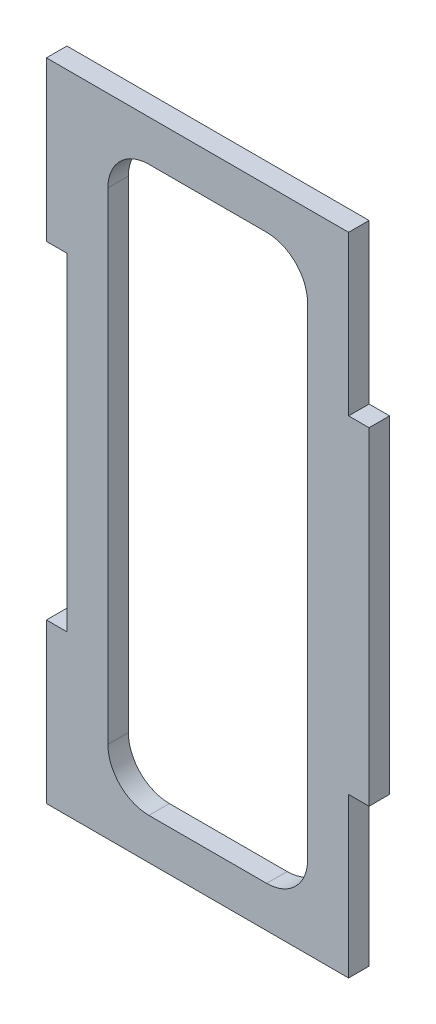
SolidWorks part; units mm, degrees
material "Acrylic (Medium-high impact)"
ref_plane "Front Plane" through (0, 0, 0) normal (0, 0, 1) x (1, 0, 0)
ref_plane "Top Plane" through (0, 0, 0) normal (0, 1, 0) x (1, 0, 0)
ref_plane "Right Plane" through (0, 0, 0) normal (1, 0, 0) x (0, 0, -1)
sketch "Sketch1" plane through (0, 0, 0) normal (0, 0, 1) x (1, 0, 0)
  line L1 (-50, -150.1518) -> (50, -150.1518)
  line L2 (-50, -150.1518) -> (-50, 50)
  line L3 (-50, 50) -> (50, 50)
  line L4 (50, -150.1518) -> (50, 50)
  dimension "D1" = 100
  dimension "D2" = 50
  dimension "D3" = 200.1518
  dimension "D4" = 50
extrude "Boss-Extrude1" add sketch "Sketch1" along normal blind 6.35
sketch "Sketch2" plane through (0, 0, 6.35) normal (0, 0, 1) x (1, 0, 0)
  line L0 (-43.65, 50) -> (-43.65, -150.1518) construction
  line L1 (50, 50) -> (-50, 50) construction
  line L2 (-50, -150.1518) -> (50, -150.1518) construction
  line L3 (-50, -50.0759) -> (50, -50.0759) construction
  line L4 (-50, 50) -> (-50, -150.1518) construction
  line L5 (50, -150.1518) -> (50, 50) construction
  line L6 (43.65, 50) -> (43.65, -150.1518) construction
  line L7 (-43.65, -50.0759) -> (-43.65, 50) construction
  line L8 (43.65, -50.0759) -> (43.65, 50) construction
  line L10 (-50, -50.0759) -> (-43.65, -50.0759)
  line L11 (-50, -50.0759) -> (-50, 0.7241)
  line L12 (-50, 0.7241) -> (-43.65, 0.7241)
  line L13 (-43.65, -50.0759) -> (-43.65, 0.7241)
  line L14 (-50, -50.0759) -> (-43.65, -50.0759)
  line L15 (-50, -50.0759) -> (-50, -100.8759)
  line L16 (-50, -100.8759) -> (-43.65, -100.8759)
  line L17 (-43.65, -50.0759) -> (-43.65, -100.8759)
  line L18 (43.65, 50) -> (50, 50)
  line L19 (43.65, 50) -> (43.65, 0.7241)
  line L20 (43.65, 0.7241) -> (50, 0.7241)
  line L21 (50, 50) -> (50, 0.7241)
  line L22 (43.65, -150.1518) -> (50, -150.1518)
  line L23 (43.65, -150.1518) -> (43.65, -100.8759)
  line L24 (43.65, -100.8759) -> (50, -100.8759)
  line L25 (50, -150.1518) -> (50, -100.8759)
  line M8 (-50, 50) -> (-50, -150.1518)
  line M9 (-50, -150.1518) -> (50, -150.1518)
  line M10 (50, -150.1518) -> (50, 50)
  line M11 (50, 50) -> (-50, 50)
  dimension "D1" = 6.35
  dimension "D2" = 6.35
  dimension "D3" = 100.0759
  dimension "D4" = 50.8
  dimension "D5" = 50.8
  dimension "D6" = 50.8
  dimension "D7" = 50.8
extrude "Cut-Extrude1" cut sketch "Sketch2" against normal blind 6.35 contours L10 L13 L12 M8 | L17 L10 L16 M8 | L19 L20 M10 M11 | L24 L23 M9 M10 region at (-46.825, -24.6759, 6.35) region at (-46.825, -75.4759, 6.35) region at (46.825, 25.3621, 6.35) region at (46.825, -125.5139, 6.35)
sketch "Sketch3" plane through (0, 0, 6.35) normal (0, 0, 1) x (1, 0, 0)
  line L0 (-43.65, -100.8759) -> (-43.65, 0.7241) construction
  line L1 (-30.95, -137.4518) -> (30.95, -137.4518)
  line L2 (-30.95, -137.4518) -> (-30.95, 37.3)
  line L3 (-30.95, 37.3) -> (30.95, 37.3)
  line L4 (30.95, -137.4518) -> (30.95, 37.3)
  line L5 (43.65, 50) -> (-50, 50) construction
  line L6 (43.65, 50) -> (43.65, 0.7241) construction
  line L7 (-50, -150.1518) -> (43.65, -150.1518) construction
  dimension "D1" = 12.7
  dimension "D2" = 12.7
  dimension "D3" = 12.7
  dimension "D4" = 12.7
extrude "Cut-Extrude2" cut sketch "Sketch3" against normal blind 6.35
fillet "Fillet1" radius 12.7 4 edges at (30.95, -137.4518, 3.175) (30.95, 37.3, 3.175) (-30.95, 37.3, 3.175) (-30.95, -137.4518, 3.175)
sketch "Sketch4" plane through (0, 0, 6.35) normal (0, 0, 1) x (1, 0, 0)
  line L0 (-30.95, 24.6) -> (-30.95, -124.7518)
  line L1 (-50, 50) -> (43.65, 50)
  line L2 (-50, 50) -> (-50, 0.7241)
  line L3 (-50, -150.1518) -> (43.65, -150.1518)
  line L4 (43.65, 50) -> (43.65, 0.7241)
  line L5 (50, -100.8759) -> (43.65, -100.8759)
  line L6 (50, -100.8759) -> (50, 0.7241)
  line L7 (50, 0.7241) -> (43.65, 0.7241)
  line L9 (-50, 0.7241) -> (-43.65, 0.7241)
  line L10 (43.65, -100.8759) -> (43.65, -150.1518)
  line L11 (-50, -100.8759) -> (-43.65, -100.8759)
  line L12 (-43.65, 0.7241) -> (-43.65, -100.8759)
  line L13 (30.95, 24.6) -> (30.95, -124.7518)
  line L14 (-18.25, 37.3) -> (18.25, 37.3)
  line L15 (18.25, -137.4518) -> (-18.25, -137.4518)
  line L16 (-50, -100.8759) -> (-50, -150.1518)
  arc A0 (-18.25, 37.3) -> (-30.95, 24.6) centre (-18.25, 24.6) ccw
  arc A1 (18.25, 37.3) -> (30.95, 24.6) centre (18.25, 24.6) cw
  arc A2 (-30.95, -124.7518) -> (-18.25, -137.4518) centre (-18.25, -124.7518) ccw
  arc A3 (18.25, -137.4518) -> (30.95, -124.7518) centre (18.25, -124.7518) ccw
